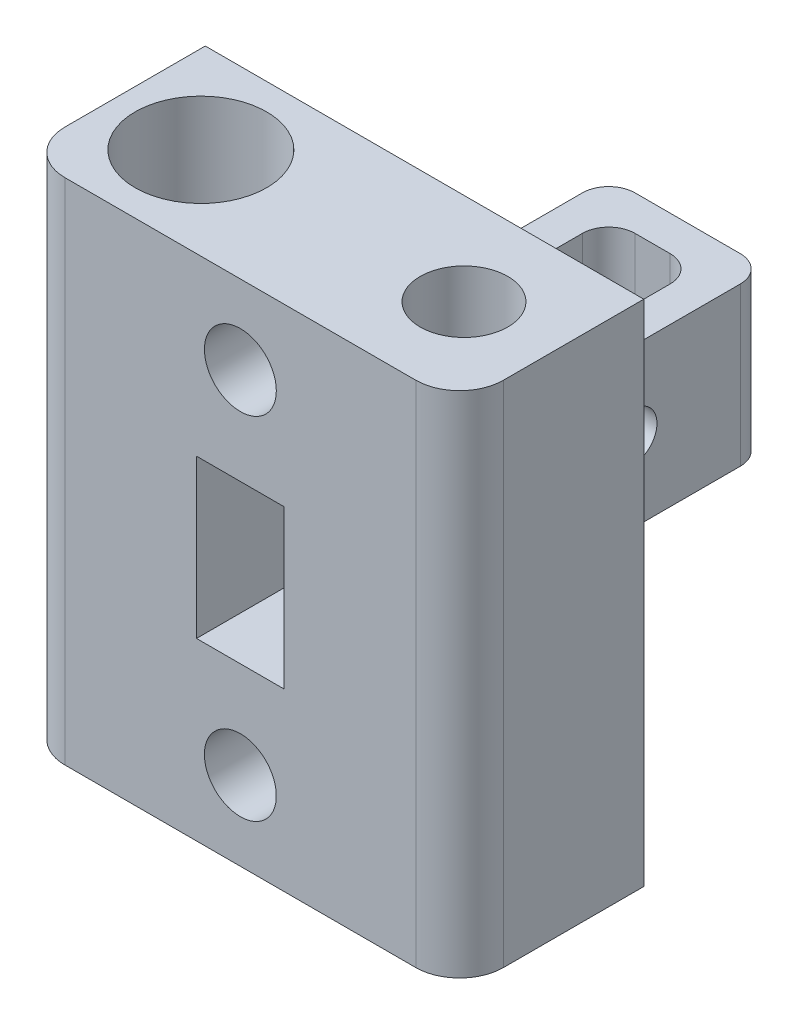
SolidWorks part; units mm, degrees
ref_plane "Front Plane" through (0, 0, 0) normal (0, 0, 1) x (1, 0, 0)
ref_plane "Top Plane" through (0, 0, 0) normal (0, 1, 0) x (1, 0, 0)
ref_plane "Right Plane" through (0, 0, 0) normal (1, 0, 0) x (0, 0, -1)
sketch "Sketch1" plane through (0, 0, 0) normal (0, 1, 0) x (1, 0, 0)
  line L1 (-25, 10.5) -> (25, 10.5)
  line L2 (-25, 10.5) -> (-25, -10.5)
  line L3 (-25, -10.5) -> (25, -10.5)
  line L4 (25, 10.5) -> (25, -10.5)
  line L5 (-25, 10.5) -> (25, -10.5) construction
  line L6 (-25, -10.5) -> (25, 10.5) construction
  point P0 (0, 0)
  dimension "D1" = 21
  dimension "D2" = 50
extrude "Boss-Extrude1" add sketch "Sketch1" along normal blind 58
sketch "Sketch3" plane through (0, 58, 0) normal (0, 1, 0) x (1, 0, 0)
  line L0 (-15, 0) -> (15, 0) construction
  circle A0 centre (-15, 0) radius 7.5
  dimension "D1" = 15
  dimension "D2" = 30
extrude "Cut-Extrude1" cut sketch "Sketch3" against normal blind 24 contours A0
sketch "Sketch4" plane through (0, 58, 0) normal (0, 1, 0) x (1, 0, 0)
  line L0 (-15, 0) -> (15, 0) construction
  circle A0 centre (15, 0) radius 5
  dimension "D1" = 10
extrude "Cut-Extrude2" cut sketch "Sketch4" against normal up to next
sketch "Sketch5" plane through (0, 0, 0) normal (0, -1, 0) x (1, 0, 0)
  circle A1 centre (-15, 0) radius 7.5
  circle A2 centre (-15, 0) radius 7.5
  dimension "D1" = 0
extrude "Cut-Extrude3" cut sketch "Sketch5" against normal blind 24
sketch "Sketch6" plane through (0, 0, 0) normal (0, -1, 0) x (1, 0, 0)
  circle A0 centre (-15, 0) radius 4.5
extrude "Cut-Extrude4" cut sketch "Sketch6" against normal up to next
sketch "Sketch7" plane through (0, 0, 10.5) normal (0, 0, 1) x (1, 0, 0)
  line L0 (0, 58) -> (0, 0) construction
  line L1 (-25, 58) -> (25, 58) construction
  line L2 (-25, 0) -> (25, 0) construction
  line L3 (-25, 29) -> (25, 29) construction
  line L4 (-25, 58) -> (-25, 0) construction
  line L5 (25, 58) -> (25, 0) construction
  circle A1 centre (0, 49) radius 4.1
  circle A2 centre (0, 9) radius 4.1
  point P24 (0, 9)
  dimension "D1" = 8.2
  dimension "D2" = 9
sketch "Sketch8" plane through (0, 0, 10.5) normal (0, 0, 1) x (1, 0, 0)
  line L0 (-25, 29) -> (25, 29) construction
  line L1 (-25, 58) -> (-25, 0) construction
  line L2 (25, 58) -> (25, 0) construction
  line L3 (0, 58) -> (0, 0) construction
  line L4 (-25, 58) -> (25, 58) construction
  line L6 (-5, 20) -> (5, 20)
  line L7 (-5, 20) -> (-5, 38)
  line L8 (-5, 38) -> (5, 38)
  line L9 (5, 20) -> (5, 38)
  line L10 (-5, 20) -> (5, 38) construction
  line L11 (-5, 38) -> (5, 20) construction
  point P11 (0, 29)
  dimension "D1" = 18
  dimension "D2" = 10
extrude "Cut-Extrude5" cut sketch "Sketch8" against normal up to next
sketch "Sketch10" plane through (0, 0, -10.5) normal (0, 0, -1) x (-1, 0, 0)
  line L0 (-25, 29) -> (25, 29) construction
  line L1 (-25, 58) -> (-25, 0) construction
  line L2 (25, 58) -> (25, 0) construction
  line L3 (0, 58) -> (0, 0) construction
  line L4 (-25, 58) -> (25, 58) construction
extrude "Cut-Extrude6" cut sketch "Sketch7" against normal blind 15
sketch "Sketch11" plane through (0, 0, -10.5) normal (0, 0, -1) x (-1, 0, 0)
  line L0 (-25, 29) -> (25, 29) construction
  line L1 (9, 38) -> (5, 38)
  line L2 (9, 38) -> (9, 20)
  line L3 (9, 20) -> (5, 20)
  line L4 (5, 38) -> (5, 20)
  line L5 (9, 38) -> (5, 20) construction
  line L6 (9, 20) -> (5, 38) construction
  line L7 (0, 58) -> (0, 0) construction
  line L8 (0, 58) -> (0, 0)
  line L9 (-9, 20) -> (-5, 20)
  line L10 (-5, 38) -> (-5, 20)
  line L11 (-9, 38) -> (-5, 38)
  line L12 (-9, 38) -> (-9, 20)
  point P0 (7, 29)
  line M7 (-5, 20) -> (-5, 38)
  line M9 (5, 38) -> (5, 20)
  dimension "D1" = 5
  dimension "D2" = 4
  dimension "D3" = 18
extrude "Boss-Extrude2" add sketch "Sketch11" along normal blind 26 contours L1 L4 L3 L2 M9 | L11 L12 L9 L10 M7 region at (-7, 29, -10.5) region at (7, 29, -10.5)
sketch "Sketch12" plane through (0, 0, -36.5) normal (0, 0, -1) x (-1, 0, 0)
  line L1 (9, 20) -> (-9, 20)
  line L2 (9, 20) -> (9, 38)
  line L3 (9, 38) -> (-9, 38)
  line L4 (-9, 20) -> (-9, 38)
extrude "Boss-Extrude3" add sketch "Sketch12" along normal blind 4
sketch "Sketch13" plane through (9, 0, 0) normal (1, 0, 0) x (0, 0, -1)
  line L3 (10.5, 29) -> (40.5, 29) construction
  line L4 (10.5, 38) -> (10.5, 20) construction
  line L5 (40.5, 38) -> (40.5, 20) construction
  line L6 (16.25, 29) -> (25.25, 29) construction
  line L7 (16.25, 31.75) -> (25.25, 31.75)
  line L8 (16.25, 26.25) -> (25.25, 26.25)
  arc A0 (16.25, 31.75) -> (16.25, 26.25) centre (16.25, 29) ccw
  arc A1 (25.25, 26.25) -> (25.25, 31.75) centre (25.25, 29) ccw
  point P1 (13.5, 29)
  point P14 (20.75, 29)
  dimension "D1" = 5.5
  dimension "D2" = 3
  dimension "D3" = 9
extrude "Cut-Extrude7" cut sketch "Sketch13" against normal through all
fillet "Fillet1" radius 5 2 edges at (-25, 29, 10.5) (25, 29, 10.5)
fillet "Fillet2" radius 5 4 edges at (-7, 20, -10.5) (7, 20, -10.5) (-7, 38, -10.5) (7, 38, -10.5)
fillet "Fillet3" radius 3 4 edges at (-5, 29, -36.5) (5, 29, -36.5) (-9, 29, -40.5) (9, 29, -40.5)
